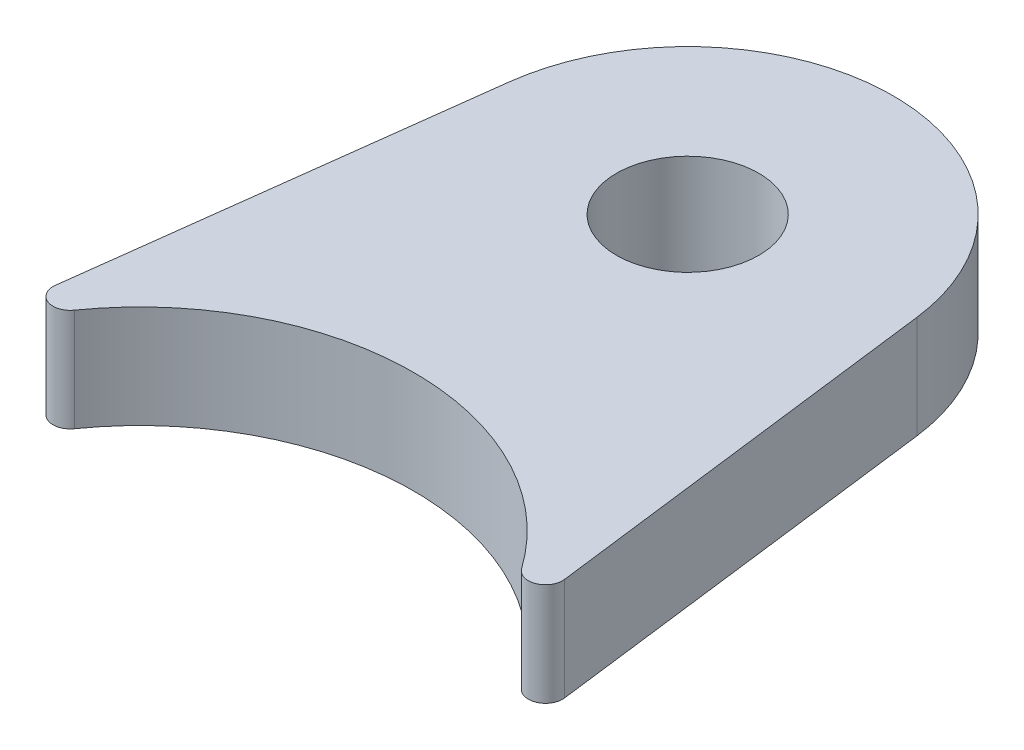
SolidWorks part; units mm, degrees
material "Alloy Steel"
ref_plane "X-Y Datum" through (0, 0, 0) normal (0, 0, 1) x (1, 0, 0)
ref_plane "X-Z Datum" through (0, 0, 0) normal (0, 1, 0) x (1, 0, 0)
ref_plane "Y-Z Datum" through (0, 0, 0) normal (1, 0, 0) x (0, 0, -1)
sketch "Sketch1" plane through (0, 0, 0) normal (0, 1, 0) x (1, 0, 0)
  line L0 (0, 0) -> (0, 25.4) construction
  line L1 (-12.6004, 1.5875) -> (-9.4503, 26.5906)
  line L2 (12.6004, 1.5875) -> (9.4503, 26.5906)
  circle A0 centre (0, 0) radius 12.7
  circle A1 centre (0, 25.4) radius 9.525
  circle A2 centre (0, 25.4) radius 3 construction
  dimension "D1" = 25.4
  dimension "D3" = 19.05
  dimension "D4" = 6
  dimension "D2" = 25.4
extrude "Boss-Extrude1" add sketch "Sketch1" along normal blind 4.7625 contours A1 | A1 L1 A0 L2 region at (0, 0, -14.296) region at (0, 0, -25.4)
fillet "Fillet1" radius 0.7937 2 edges at (12.6004, 2.3813, -1.5875) (-12.6004, 2.3813, -1.5875)
hole_wizard "M6 Clearance Hole1" positions "Sketch2" profile "Sketch3" hole size "M6" standard "ANSI Metric" end condition through all
sketch "Sketch2" plane through (0, 4.7625, 0) normal (0, 1, 0) x (1, 0, 0)
  point P0 (0, 25.4)
sketch "Sketch3" plane through (0, 4.7625, -25.4) normal (1, 0, 0) x (0, 0, 1)
  line L0 (0, 0) -> (0, 4.7625)
  line L1 (0, 4.7625) -> (3.3, 4.7625)
  line L2 (3.3, 4.7625) -> (3.3, 0)
  line L5 (3.3, 0) -> (0, 0)
  line L11 (0, -6.35) -> (0, 107.95) construction
  dimension "Thru Hole Dia." = 6.6
  dimension "Thru Hole Depth" = 4.7625
